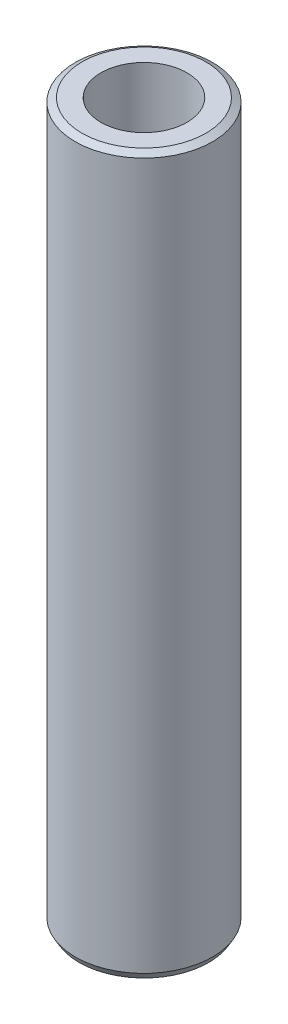
SolidWorks part; units mm, degrees
ref_plane "Front Plane" through (0, 0, 0) normal (0, 0, 1) x (1, 0, 0)
ref_plane "Top Plane" through (0, 0, 0) normal (0, 1, 0) x (1, 0, 0)
ref_plane "Right Plane" through (0, 0, 0) normal (1, 0, 0) x (0, 0, -1)
sketch "Sketch1" plane through (0, 0, 0) normal (0, 1, 0) x (1, 0, 0)
  circle A0 centre (0, 0) radius 57.5
  dimension "SHAFT_OD" = 115
extrude "Boss-Extrude1" add sketch "Sketch1" along normal blind 600
sketch "Sketch2" plane through (0, 0, 0) normal (0, 1, 0) x (1, 0, 0)
  circle A0 centre (0, 0) radius 36.0158
  dimension "BORE_D" = 72.0316
extrude "Cut-Extrude1" cut sketch "Sketch2" along normal through all
chamfer "Chamfer1" distance 3.2793 angle 60 2 edges at (0, 600, 57.5) (0, 0, 57.5) first distance on face at (0, 600, 57.5) first distance on face at (0, 0, 36.0158)
